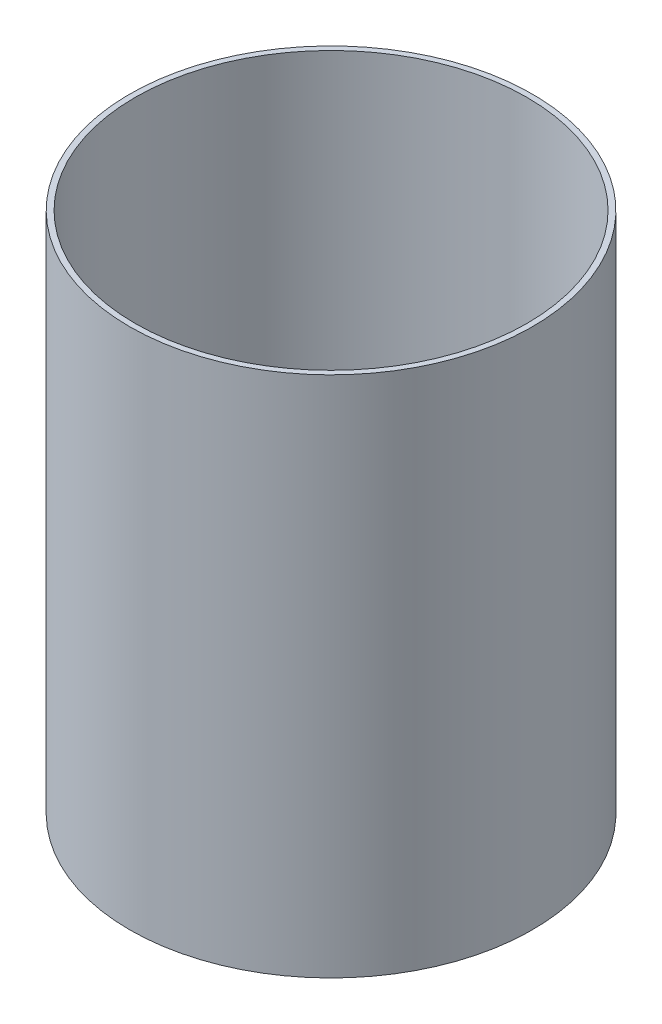
SolidWorks part; units mm, degrees
ref_plane "Front Plane" through (0, 0, 0) normal (0, 0, 1) x (1, 0, 0)
ref_plane "Top Plane" through (0, 0, 0) normal (0, 1, 0) x (1, 0, 0)
ref_plane "Right Plane" through (0, 0, 0) normal (1, 0, 0) x (0, 0, -1)
sketch "Sketch1" plane through (0, 0, 0) normal (0, 1, 0) x (1, 0, 0)
  circle A0 centre (0, 0) radius 76.2
  circle A1 centre (0, 0) radius 78.359
  dimension "D1" = 152.4
  dimension "D2" = 156.718
extrude "Boss-Extrude1" add sketch "Sketch1" along normal blind 203.2
equation "\"Length\"= 8"
equation "\"D1@Boss-Extrude1\"=\"Length\""
